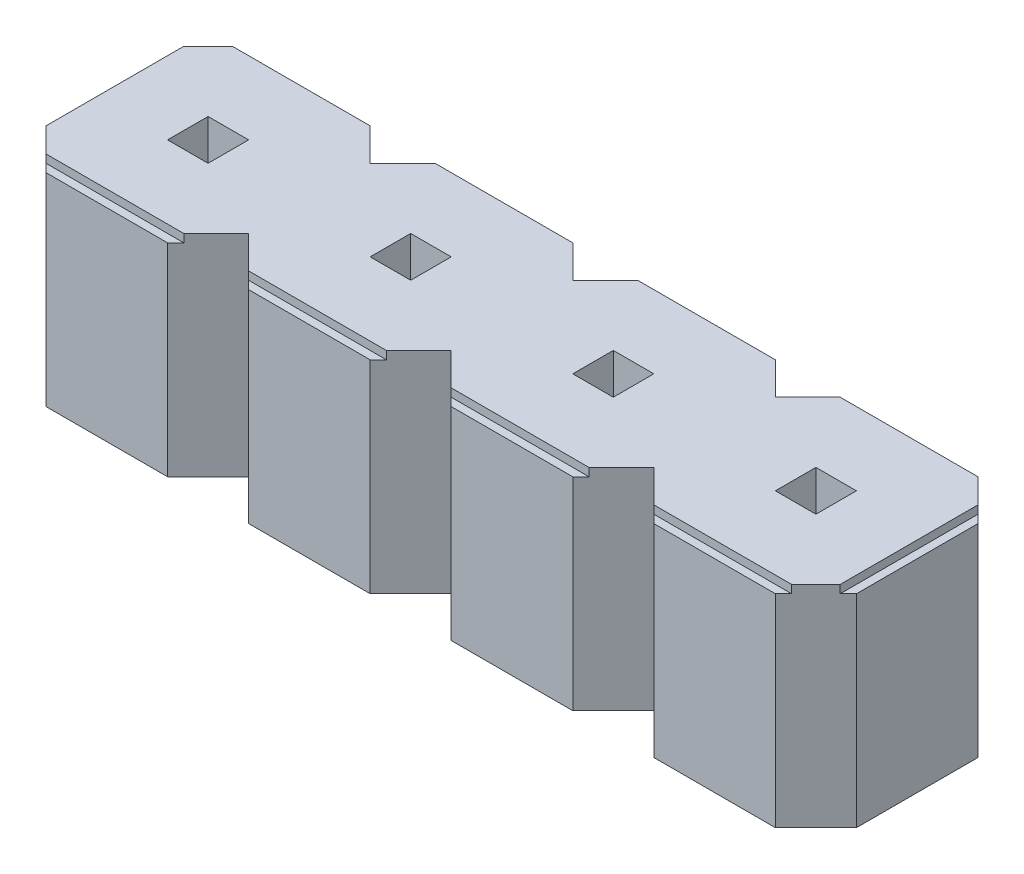
SolidWorks part; units mm, degrees
ref_plane "Front Plane" through (0, 0, 0) normal (0, 0, 1) x (1, 0, 0)
ref_plane "Top Plane" through (0, 0, 0) normal (0, 1, 0) x (1, 0, 0)
ref_plane "Right Plane" through (0, 0, 0) normal (1, 0, 0) x (0, 0, -1)
sketch "Sketch1" plane through (0, 0, 0) normal (0, 1, 0) x (1, 0, 0)
  line L0 (-1.25, 0.75) -> (-0.75, 1.25)
  line L1 (-0.75, -1.25) -> (0.75, -1.25)
  line L2 (-1.25, -0.75) -> (-1.25, 0.75)
  line L3 (-0.75, 1.25) -> (0.75, 1.25)
  line L5 (-1.25, -1.25) -> (-1, -1) construction
  line L6 (-1.25, 1.25) -> (-1, 1) construction
  line L7 (0.75, 1.25) -> (1.25, 0.75)
  line L8 (0.75, -1.25) -> (1.25, -0.75)
  line L9 (-1.25, -0.75) -> (-0.75, -1.25)
  line L10 (1.75, 1.25) -> (3.25, 1.25)
  line L12 (3.25, 1.25) -> (3.75, 0.75)
  line L13 (1.25, 0.75) -> (1.75, 1.25)
  line L15 (1.25, -0.75) -> (1.75, -1.25)
  line L16 (1.75, -1.25) -> (3.25, -1.25)
  line L17 (3.25, -1.25) -> (3.75, -0.75)
  line L18 (4.25, 1.25) -> (5.75, 1.25)
  line L20 (5.75, 1.25) -> (6.25, 0.75)
  line L21 (3.75, 0.75) -> (4.25, 1.25)
  line L23 (3.75, -0.75) -> (4.25, -1.25)
  line L24 (4.25, -1.25) -> (5.75, -1.25)
  line L25 (5.75, -1.25) -> (6.25, -0.75)
  line L26 (6.75, 1.25) -> (8.25, 1.25)
  line L27 (8.75, -0.75) -> (8.75, 0.75)
  line L28 (8.25, 1.25) -> (8.75, 0.75)
  line L29 (6.25, 0.75) -> (6.75, 1.25)
  line L31 (6.25, -0.75) -> (6.75, -1.25)
  line L32 (6.75, -1.25) -> (8.25, -1.25)
  line L33 (8.25, -1.25) -> (8.75, -0.75)
  line L34 (1.25, -0.75) -> (1.25, 0.75) [skipped]
  line L35 (3.75, -0.75) -> (3.75, 0.75) [skipped]
  line L36 (6.25, -0.75) -> (6.25, 0.75) [skipped]
  line L37 (1, 1) -> (1.25, 1.25) construction
  line L38 (1, -1) -> (1.25, -1.25) construction
  line L39 (2.25, 0.25) -> (2.75, 0.25) construction
  line L40 (-0.25, -0.25) -> (0.25, -0.25) construction
  line L41 (-0.25, -0.25) -> (-0.25, 0.25) construction
  line L42 (-0.25, 0.25) -> (0.25, 0.25) construction
  line L43 (0.25, -0.25) -> (0.25, 0.25) construction
  line L44 (-0.25, -0.25) -> (0.25, 0.25) construction
  line L45 (-0.25, 0.25) -> (0.25, -0.25) construction
  line L46 (2.75, -0.25) -> (2.75, 0.25) construction
  line L47 (2.25, -0.25) -> (2.75, -0.25) construction
  line L48 (2.25, -0.25) -> (2.25, 0.25) construction
  line L49 (4.75, 0.25) -> (5.25, 0.25) construction
  line L50 (5.25, -0.25) -> (5.25, 0.25) construction
  line L51 (4.75, -0.25) -> (5.25, -0.25) construction
  line L52 (4.75, -0.25) -> (4.75, 0.25) construction
  line L53 (7.25, 0.25) -> (7.75, 0.25) construction
  line L54 (7.75, -0.25) -> (7.75, 0.25) construction
  line L55 (7.25, -0.25) -> (7.75, -0.25) construction
  line L56 (7.25, -0.25) -> (7.25, 0.25) construction
  line L57 (-1.25, -0.75) -> (1.25, -0.75)
  line L58 (3.75, -0.75) -> (6.25, -0.75)
  line L59 (8.75, -0.75) -> (6.25, -0.75)
  point P0 (0, 0)
  point P14 (0, 0)
  point P47 (2.5, 0.25)
  point P48 (2.5, 1.25)
  dimension "D1" = 2.5
  dimension "D2" = 4
  dimension "D3" = 0.5
  dimension "D9" = 2.5
  dimension "D8" = 4
extrude "Boss-Extrude1" add sketch "Sketch1" along normal mid plane 2.6 contours L58 L23 L24 L25 | L33 L59 L31 L32 | L59 L27 L28 L26 L29 L20 L18 L21 L12 L10 L13 L7 L3 L0 L2 L57 L15 L16 L17 L58 | L57 L9 L1 L8 region at (0, 0, -0.2061) region at (0, 0, 0.9792) region at (2.5, 0, 0) region at (5, 0, 0.9792) region at (5, 0, -0.2061) region at (7.5, 0, 0.9792) region at (7.5, 0, -0.2061)
sketch "Sketch2" plane through (0, 1.3, 0) normal (0, 1, 0) x (1, 0, 0)
  line L0 (3.75, 0.75) -> (3.75, -0.75) construction
  line L2 (-1.15, -1.15) -> (8.65, -1.15)
  line L3 (-1.15, -1.15) -> (-1.15, 1.15)
  line L4 (-1.15, 1.15) -> (8.65, 1.15)
  line L5 (8.65, -1.15) -> (8.65, 1.15)
  line L6 (-1.15, -1.15) -> (8.65, 1.15) construction
  line L7 (-1.15, 1.15) -> (8.65, -1.15) construction
  line L8 (-2.0486, -2.0847) -> (9.5486, -2.0847)
  line L9 (-2.0486, -2.0847) -> (-2.0486, 2.0847)
  line L10 (-2.0486, 2.0847) -> (9.5486, 2.0847)
  line L11 (9.5486, -2.0847) -> (9.5486, 2.0847)
  line L12 (-2.0486, -2.0847) -> (9.5486, 2.0847) construction
  line L13 (-2.0486, 2.0847) -> (9.5486, -2.0847) construction
  point P4 (3.75, 0)
  point P9 (3.75, 0)
  dimension "D1" = 9.8
  dimension "D2" = 2.3
extrude "Cut-Extrude1" cut sketch "Sketch2" against normal blind 0.1
sketch "Sketch3" plane through (0, 1.3, 0) normal (0, 1, 0) x (1, 0, 0)
  line L0 (2.25, 0.25) -> (2.75, 0.25)
  line L1 (-0.25, -0.25) -> (0.25, -0.25)
  line L2 (-0.25, -0.25) -> (-0.25, 0.25)
  line L3 (-0.25, 0.25) -> (0.25, 0.25)
  line L4 (0.25, -0.25) -> (0.25, 0.25)
  line L5 (-0.25, -0.25) -> (0.25, 0.25) construction
  line L6 (-0.25, 0.25) -> (0.25, -0.25) construction
  line L7 (2.75, -0.25) -> (2.75, 0.25)
  line L8 (2.25, -0.25) -> (2.25, 0.25)
  line L9 (2.25, -0.25) -> (2.75, -0.25)
  line L10 (4.75, 0.25) -> (5.25, 0.25)
  line L11 (5.25, -0.25) -> (5.25, 0.25)
  line L12 (4.75, -0.25) -> (4.75, 0.25)
  line L13 (4.75, -0.25) -> (5.25, -0.25)
  line L14 (7.25, 0.25) -> (7.75, 0.25)
  line L15 (7.75, -0.25) -> (7.75, 0.25)
  line L16 (7.25, -0.25) -> (7.25, 0.25)
  line L17 (7.25, -0.25) -> (7.75, -0.25)
  point P0 (0, 0)
  dimension "D1" = 0.5
  dimension "D2" = 0.5
  dimension "D3" = 4
extrude "Cut-Extrude2" cut sketch "Sketch3" against normal through all
